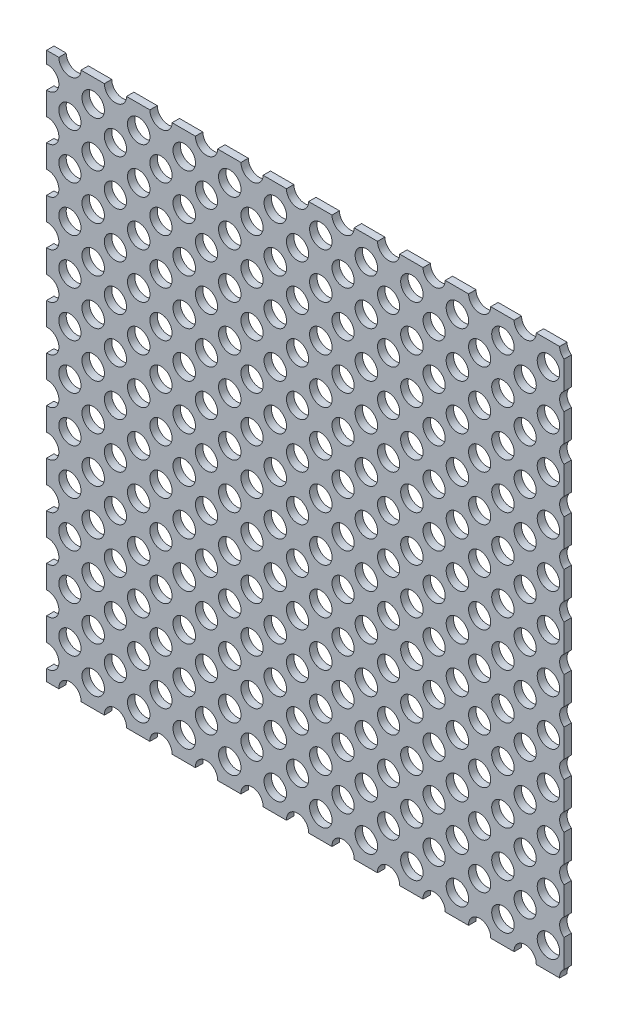
SolidWorks part; units mm, degrees
material "6061 Alloy"
ref_plane "Front Plane" through (0, 0, 0) normal (0, 0, 1) x (1, 0, 0)
ref_plane "Top Plane" through (0, 0, 0) normal (0, 1, 0) x (1, 0, 0)
ref_plane "Right Plane" through (0, 0, 0) normal (1, 0, 0) x (0, 0, -1)
sketch "Sketch1" plane through (0, 0, 0) normal (0, 0, 1) x (1, 0, 0)
  line L1 (-111.125, 117.475) -> (111.125, 117.475)
  line L2 (-111.125, 117.475) -> (-111.125, -117.475)
  line L3 (-111.125, -117.475) -> (111.125, -117.475)
  line L4 (111.125, 117.475) -> (111.125, -117.475)
  line L5 (-111.125, 117.475) -> (111.125, -117.475) construction
  line L6 (-111.125, -117.475) -> (111.125, 117.475) construction
  point P0 (0, 0)
  dimension "D1" = 222.25
  dimension "D2" = 234.95
extrude "Boss-Extrude1" add sketch "Sketch1" against normal blind 3.175
sketch "Sketch2" plane through (0, 0, 0) normal (0, 0, 1) x (1, 0, 0)
  line L0 (-111.125, 117.475) -> (-111.125, -117.475) construction
  line L2 (111.125, 117.475) -> (-111.125, 117.475) construction
  circle A0 centre (-101.125, 117.475) radius 4.7625
  circle A1 centre (-91.125, 107.475) radius 4.826
  dimension "D1" = 9.525
  dimension "D2" = 10
  dimension "D4" = 9.652
  dimension "D5" = 10
  dimension "D6" = 10
extrude "Cut-Extrude1" cut sketch "Sketch2" against normal blind 3.175
pattern_linear "LPattern1" count 16 spacing 19.558 along (1, 0, 0) count 2 spacing 19.558 along (-1, 0, 0) of "Cut-Extrude1" pattern seed only yes
pattern_linear "LPattern2" count 16 spacing 19.558 along (0, -1, 0) of "LPattern1"
